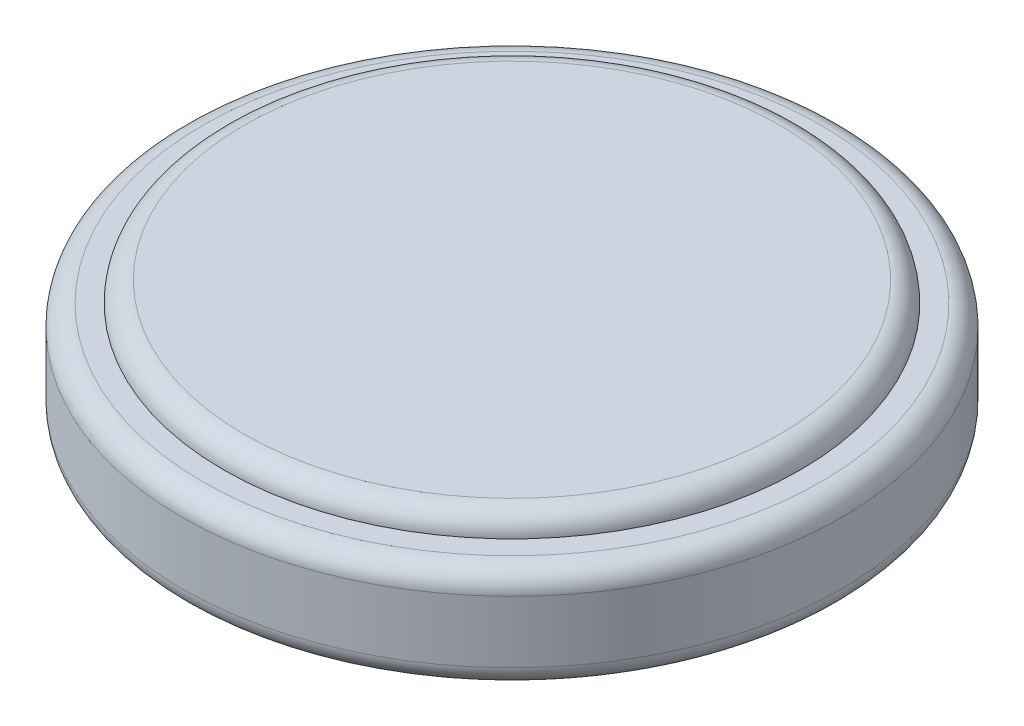
SolidWorks part; units mm, degrees
ref_plane "Front Plane" through (0, 0, 0) normal (0, 0, 1) x (1, 0, 0)
ref_plane "Top Plane" through (0, 0, 0) normal (0, 1, 0) x (1, 0, 0)
ref_plane "Right Plane" through (0, 0, 0) normal (1, 0, 0) x (0, 0, -1)
sketch "Sketch1" plane through (0, 0, 0) normal (0, 1, 0) x (1, 0, 0)
  circle A0 centre (0, 0) radius 8
  dimension "D1" = 16
extrude "Boss-Extrude1" add sketch "Sketch1" along normal blind 2.5
sketch "Sketch2" plane through (0, 2.5, 0) normal (0, 1, 0) x (1, 0, 0)
  circle A0 centre (0, 0) radius 7
  dimension "D1" = 14
extrude "Boss-Extrude2" add sketch "Sketch2" along normal blind 0.5
fillet "Fillet1" radius 0.5 3 edges at (0, 0, 8) (0, 2.5, 8) (0, 3, 7)
